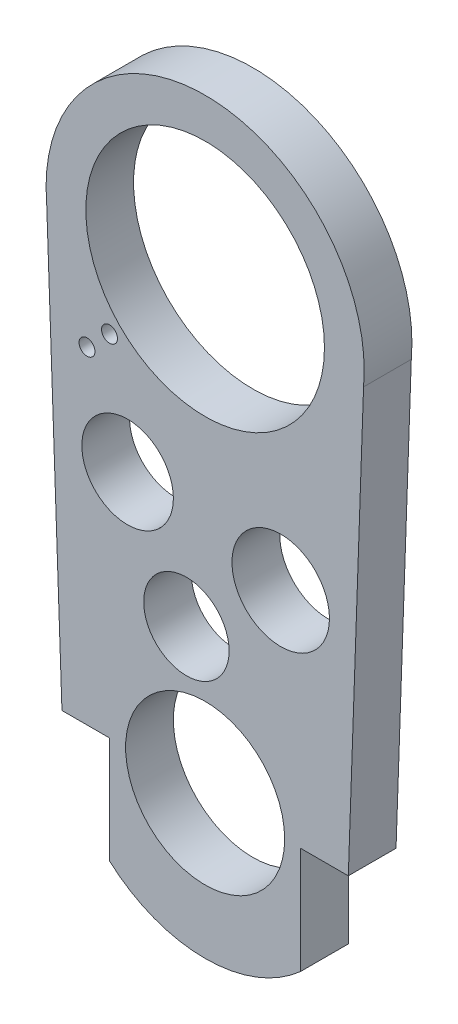
SolidWorks part; units mm, degrees
ref_plane "Plan de face" through (0, 0, 0) normal (0, 0, 1) x (1, 0, 0)
ref_plane "Plan de dessus" through (0, 0, 0) normal (0, 1, 0) x (1, 0, 0)
ref_plane "Plan de droite" through (0, 0, 0) normal (1, 0, 0) x (0, 0, -1)
sketch "Esquisse1" plane through (0, 0, 0) normal (0, 0, 1) x (1, 0, 0)
  line L0 (8.3168, 9) -> (0, 9) construction
  line L1 (0, 9) -> (0, 6) construction
  line L2 (0, 6) -> (8.0445, 6) construction
  line L3 (0, 0) -> (0, 28) construction
  line L4 (-7.5, 0) -> (-9.9591, 27.0962) construction
  line L5 (9.9591, 27.0962) -> (7.5, 0) construction
  line L6 (9.9591, 27.0962) -> (8.3168, 9) construction
  line L7 (8.0445, 6) -> (7.5, 0) construction
  line L8 (0, 0) -> (18.0723, 0) construction
  line L9 (7.5, 0) -> (6.6832, -9) construction
  line L12 (6.6832, -9) -> (0, -9) construction
  line L13 (0, -9) -> (0, -6) construction
  line L14 (0, -6) -> (-6.9555, -6) construction
  line L15 (-6.9555, -6) -> (-7.5, 0) construction
  line L16 (6, -6.7082) -> (6, 0)
  line L17 (6, 0) -> (9, 0)
  line L18 (9, 0) -> (9.9591, 27.0962)
  line L20 (-9, 0) -> (-9.9591, 27.0962)
  line L22 (-6, -6.7082) -> (-6, 0)
  line L23 (-6, 0) -> (-9, 0)
  line L24 (-7.4246, 20.5754) -> (0, 28) construction
  circle A0 centre (0, 0) radius 5
  circle A1 centre (0, 28) radius 10 construction
  arc A2 (-9.9591, 27.0962) -> (9.9591, 27.0962) centre (0, 28) cw
  arc A4 (9, 0) -> (-9, 0) centre (0, 0) cw construction
  arc A5 (-6, -6.7082) -> (6, -6.7082) centre (0, 0) ccw
  circle A6 centre (-4.8742, 15.0481) radius 2.8775
  circle A7 centre (4.7507, 13.4162) radius 3.0635
  circle A8 centre (-1.1774, 8.4871) radius 2.6843
  circle A9 centre (-7.4246, 20.5754) radius 0.5
  circle A10 centre (-6.0104, 21.9896) radius 0.5
  circle A11 centre (0, 28) radius 9 construction
  circle A12 centre (0, 36.5) radius 0.5 construction
  circle A13 centre (0, 28) radius 7.5
  dimension "D1" = 10
  dimension "D4" = 10
  dimension "D13" = 1
  dimension "D14" = 1
  dimension "D17" = 15
  dimension "D2" = 3
  dimension "D3" = 9
  dimension "D7" = 28
  dimension "D5" = 15
  dimension "D6" = 15
  dimension "D8" = 9
  dimension "D9" = 3
  dimension "D10" = 3
  dimension "D12" = 6
  dimension "D11" = 1
  dimension "D15" = 45
  dimension "D16" = 27.1131
extrude "Boss.-Extru.1" add sketch "Esquisse1" along normal blind 3
equation "\"D8@Esquisse1\"=\"D3@Esquisse1\""
equation "\"D9@Esquisse1\"=\"D2@Esquisse1\""
